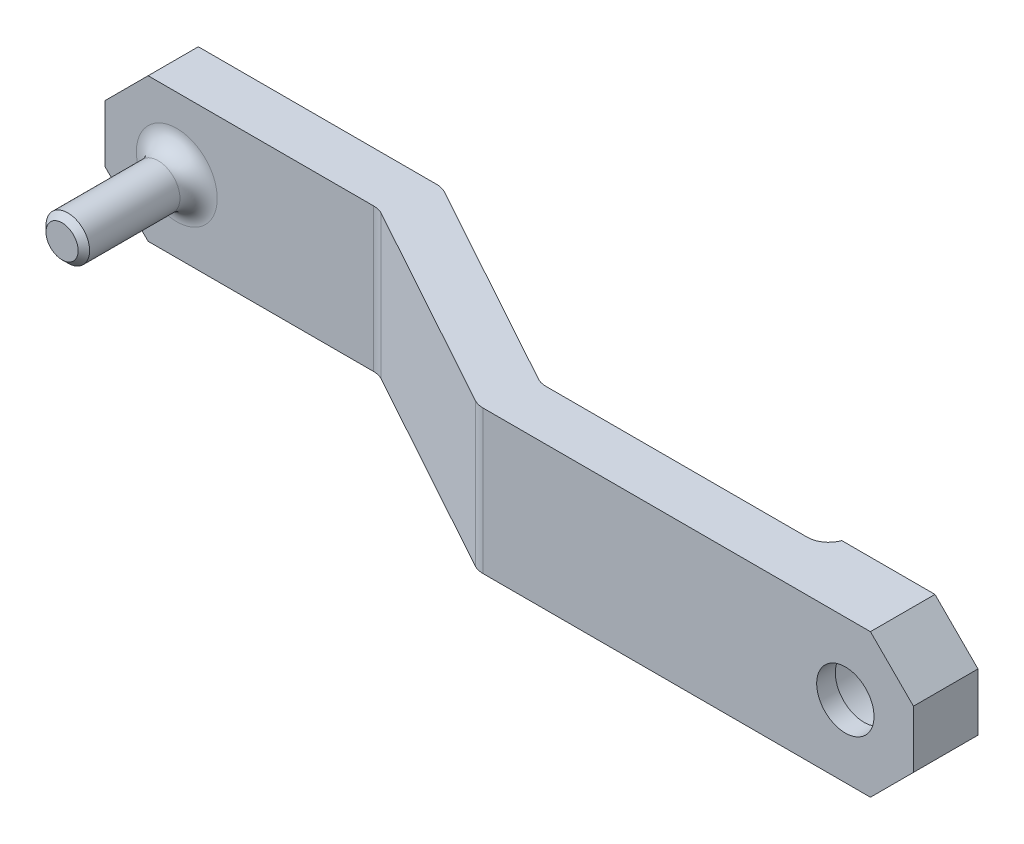
SolidWorks part; units mm, degrees
material "PLA"
ref_plane "Front Plane" through (0, 0, 0) normal (0, 0, 1) x (1, 0, 0)
ref_plane "Top Plane" through (0, 0, 0) normal (0, 1, 0) x (1, 0, 0)
ref_plane "Right Plane" through (0, 0, 0) normal (1, 0, 0) x (0, 0, -1)
sketch "Sketch1" plane through (0, 0, 0) normal (0, 1, 0) x (1, 0, 0)
  line L0 (0, 0) -> (0, -4.445)
  line L1 (0, -4.445) -> (24.2582, -4.445)
  line L2 (24.2582, -4.445) -> (43.6257, -15.0975)
  line L3 (43.6257, -15.0975) -> (82.2325, -15.0975)
  line L4 (82.2325, -15.0975) -> (82.2325, -9.3825)
  line L5 (82.2325, -9.3825) -> (70.1675, -9.3825)
  line L6 (70.1675, -9.3825) -> (70.1675, -10.6525)
  line L7 (70.1675, -10.6525) -> (44.7675, -10.6525)
  line L8 (44.7675, -10.6525) -> (25.4, 0)
  line L9 (25.4, 0) -> (0, 0)
  line L10 (76.2, -9.3825) -> (76.2, -12.3825) construction
  line L11 (6.35, 0) -> (6.35, -4.445) construction
  line L12 (100.0125, -12.3825) -> (76.2, -12.3825) construction
  line L13 (0, -2.2225) -> (6.35, -2.2225) construction
  dimension "D1" = 12.065
  dimension "D2" = 6.35
  dimension "D3" = 69.85
  dimension "D4" = 10.16
  dimension "D5" = 5.715
  dimension "D6" = 4.445
  dimension "D7" = 4.445
  dimension "D8" = 4.445
  dimension "D9" = 25.4
  dimension "D10" = 25.4
  dimension "D11" = 3
extrude "Boss-Extrude1" add sketch "Sketch1" along normal blind 12.7
sketch "Sketch2" plane through (0, 0, 9.3825) normal (0, 0, -1) x (-1, 0, 0)
  line L0 (-76.2, 12.7) -> (-76.2, 0) construction
  line L1 (-82.2325, 12.7) -> (-70.1675, 12.7) construction
  line L2 (-82.2325, 0) -> (-70.1675, 0) construction
  circle A0 centre (-76.2, 6.35) radius 4.1021
  dimension "D1" = 8.2042
extrude "Cut-Extrude1" cut sketch "Sketch2" against normal blind 4.064
sketch "Sketch3" plane through (0, 0, 13.4465) normal (0, 0, -1) x (-1, 0, 0)
  circle A0 centre (-76.2, 6.35) radius 2.54
  dimension "D1" = 5.08
extrude "Cut-Extrude2" cut sketch "Sketch3" against normal through all
sketch "Sketch4" plane through (0, 0, 4.445) normal (0, 0, -1) x (-1, 0, 0)
  line L0 (0, 6.35) -> (-6.35, 6.35) construction
  line L1 (0, 12.7) -> (0, 0) construction
  circle A0 centre (-6.35, 6.35) radius 1.9304
  dimension "D2" = 3.8608
  dimension "D1" = 6.35
extrude "Boss-Extrude2" add sketch "Sketch4" against normal blind 10.16
fillet "Fillet1" radius 1.651 1 edges at (4.4196, 6.35, 4.445)
chamfer "Chamfer1" distance 3.81 angle 45 4 edges at (82.2325, 0, 12.24) (82.2325, 12.7, 12.24) (0, 0, 2.2225) (0, 12.7, 2.2225)
fillet "Fillet2" radius 1.905 5 edges at (43.6257, 6.35, 15.0975) (24.2582, 6.35, 4.445) (25.4, 6.35, 0) (44.7675, 6.35, 10.6525) (70.1675, 6.35, 10.6525)
chamfer "Chamfer2" distance 0.635 angle 45 1 edges at (72.0979, 6.35, 9.3825)
chamfer "Chamfer3" distance 0.508 angle 45 1 edges at (4.4196, 6.35, 14.605)
